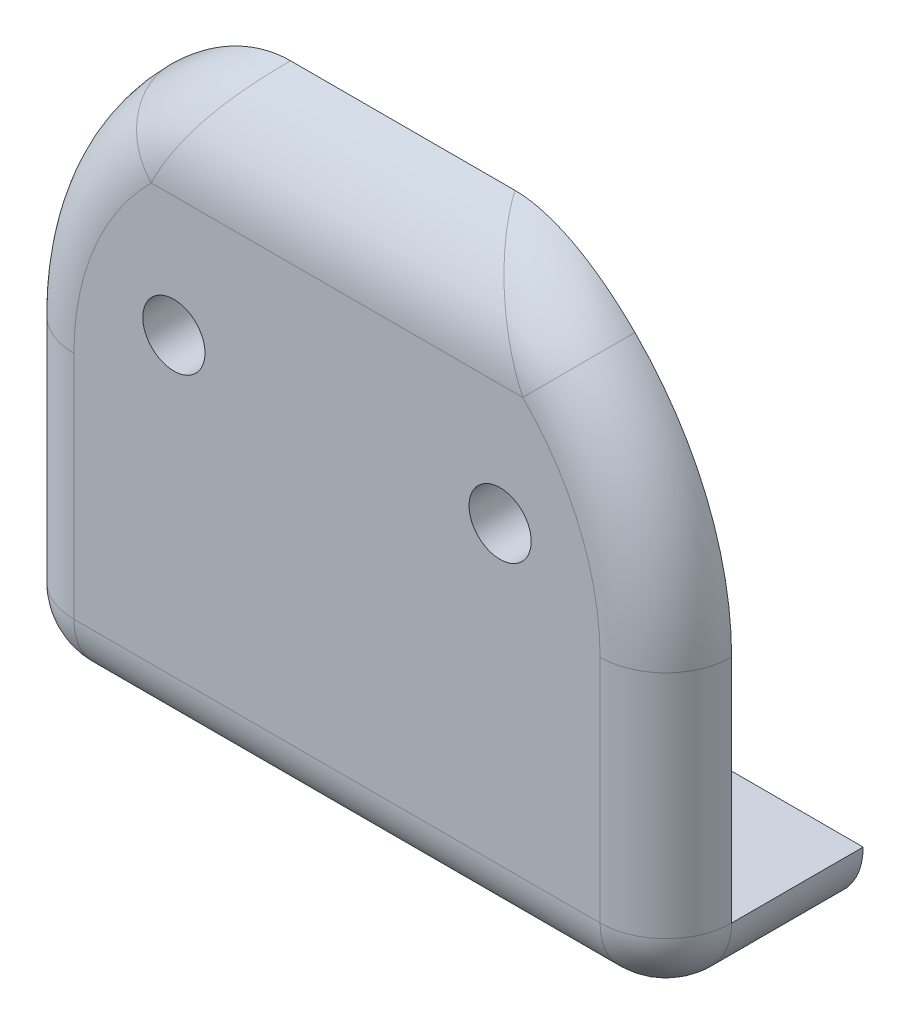
SolidWorks part; units mm, degrees
ref_plane "Front Plane" through (0, 0, 0) normal (0, 0, 1) x (1, 0, 0)
ref_plane "Top Plane" through (0, 0, 0) normal (0, 1, 0) x (1, 0, 0)
ref_plane "Right Plane" through (0, 0, 0) normal (1, 0, 0) x (0, 0, -1)
sketch "Sketch1" plane through (0, 0, 0) normal (1, 0, 0) x (0, 0, -1)
  line L0 (-3.175, 25.4) -> (-3.175, -3.175)
  line L1 (-3.175, -3.175) -> (31.75, -3.175)
  line L2 (31.75, -3.175) -> (31.75, 0)
  line L3 (31.75, 0) -> (0, 0)
  line L4 (0, 0) -> (0, 25.4)
  line L5 (0, 25.4) -> (-3.175, 25.4)
  dimension "D1" = 3.175
  dimension "D2" = 3.175
  dimension "D3" = 25.4
  dimension "D4" = 31.75
extrude "Boss-Extrude1" add sketch "Sketch1" along normal blind 31.75
fillet "Fillet1" radius 6 2 edges at (15.875, 25.4, 3.175) (15.875, -3.175, -31.75)
sketch "Sketch2" plane through (0, 0, 3.175) normal (0, 0, 1) x (1, 0, 0)
  line L0 (8.001, 14.2875) -> (23.749, 14.2875) construction
  line L1 (31.75, -3.175) -> (0, -3.175) construction
  line L2 (31.75, 20.1067) -> (31.75, -3.175) construction
  line L3 (15.875, 25.4) -> (15.875, -3.175) construction
  line L4 (0, 20.1067) -> (0, -3.175) construction
  line L5 (31.75, 25.4) -> (0, 25.4) construction
  line L7 (0, 11.1125) -> (0, 25.4)
  line L8 (0, 25.4) -> (31.75, 25.4)
  line L9 (31.75, 25.4) -> (31.75, 11.1125)
  circle A0 centre (8.001, 14.2875) radius 1.5
  circle A1 centre (23.749, 14.2875) radius 1.5
  arc A2 (31.75, 11.1125) -> (0, 11.1125) centre (15.875, 11.1125) ccw
  point P4 (15.875, 14.2875)
  point P7 (15.875, -3.175)
  point P9 (15.875, 11.1125)
  line M3 (31.75, -3.175) -> (31.75, 20.1067)
  line M4 (31.75, 20.1067) -> (0, 20.1067)
  line M5 (0, 20.1067) -> (0, -3.175)
  dimension "D1" = 3
  dimension "D2" = 15.748
  dimension "D3" = 14.2875
extrude "Cut-Extrude1" cut sketch "Sketch2" against normal through all contours A0 | A1 | A2 L9 L8 M4 | A2 M3 M4 | A2 L8 L7 M4 | A2 M4 M5 | L8 A2 region at (0.8238, 17.8996, 3.175) region at (2.9492, 23.2467, 3.175) region at (15.875, 26.0378, 3.175) region at (30.9262, 17.8996, 3.175) region at (28.8008, 23.2467, 3.175) region at (8.001, 14.2875, 3.175) region at (23.749, 14.2875, 3.175)
sketch "Sketch3" plane through (0, -3.175, 0) normal (0, -1, 0) x (1, 0, 0)
  line L0 (8.001, -19.05) -> (23.749, -19.05) construction
  line L1 (31.75, 3.175) -> (0, 3.175) construction
  line L2 (15.875, -31.75) -> (15.875, 3.175) construction
  line L4 (31.75, -31.75) -> (0, -31.75) construction
  line L5 (31.75, 3.175) -> (31.75, -26.4567) construction
  line L6 (31.75, -31.75) -> (31.75, -14.2875)
  line L7 (31.75, -31.75) -> (0, -31.75)
  line L8 (0, -31.75) -> (0, -14.2875)
  circle A0 centre (8.001, -19.05) radius 1.5
  circle A1 centre (23.749, -19.05) radius 1.5
  arc A2 (0, -14.2875) -> (31.75, -14.2875) centre (15.875, -14.2875) ccw
  point P4 (15.875, -19.05)
  point P18 (15.875, 3.175)
  line M3 (0, 3.175) -> (0, -26.4567)
  line M4 (0, -26.4567) -> (31.75, -26.4567)
  line M5 (31.75, -26.4567) -> (31.75, 3.175)
  dimension "D1" = 3
  dimension "D2" = 15.748
  dimension "D3" = 19.05
extrude "Cut-Extrude2" cut sketch "Sketch3" against normal through all contours A2 L8 L7 L6 M4 | A2 M4 M5 | A2 M3 M4 region at (15.875, -3.175, -31.4281) region at (30.1148, -3.175, -23.534) region at (1.6352, -3.175, -23.534)
fillet "Fillet2" radius 3.175 1 edges at (15.875, -3.175, 3.175)
fillet "Fillet3" radius 3.175 12 edges at (13.5464, -2.0237, -29.9908) (30.2599, -3.175, -21.0024) (31.75, -3.175, -7.1438) (31.75, -2.2451, 2.2451) (31.75, 5.5563, 3.175) (31.0355, 15.8215, 3.175) (0.7145, 15.8215, 3.175) (0, 5.5563, 3.175) (0, -2.2451, 2.2451) (0, -3.175, -7.1438) (1.4901, -3.175, -21.0024) (27.0209, 22.4167, 2.7125)
extrude "Boss-Extrude2" add sketch "Sketch3<3>" against normal blind 9.525 contours A1 | A0 region at (8.001, -3.175, -19.05) region at (23.749, -3.175, -19.05)
sketch "Sketch3<3>" plane through (0, -3.175, 0) normal (0, -1, 0) x (1, 0, 0) same geometry as "Sketch3"
sketch "Sketch4" plane through (0, -3.175, 0) normal (0, -1, 0) x (1, 0, 0)
  line L5 (0, -6.35) -> (31.75, -6.35)
  line L6 (0, -14.2875) -> (0, 0) construction
  line L7 (31.75, -14.2875) -> (31.75, 0) construction
  line L8 (31.75, -6.35) -> (31.75, -30.1621)
  line L9 (31.75, -30.1621) -> (0, -30.1621)
  line L10 (0, -30.1621) -> (0, -6.35)
  line L11 (31.75, 0) -> (0, 0) construction
  spline S0 degree 3 poles (20.4167, -29.499) (18.9343, -29.9416) (17.4245, -30.1608) (15.5041, -30.1624) (15.117, -30.1487) (14.3475, -30.0933) (13.9652, -30.0517) (12.8252, -29.8857) (12.0745, -29.7203) (11.3333, -29.499) knots 0 0 0 0 0.5 0.5 0.625 0.625 0.75 0.75 1 1 1 1 construction
  dimension "D1" = 6.35
extrude "Cut-Extrude3" cut sketch "Sketch4" against normal through all
